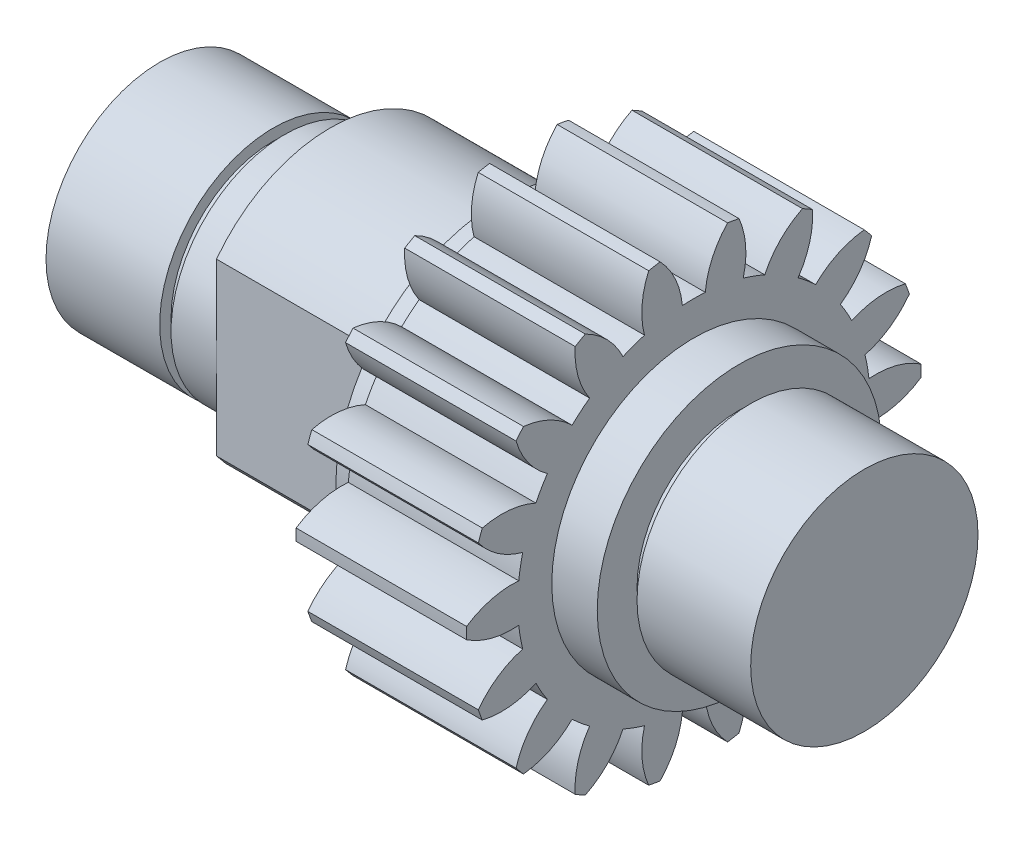
SolidWorks part; units mm, degrees
ref_plane "Plane1" through (0, 0, 0) normal (0, 0, 1) x (1, 0, 0)
ref_plane "Plane2" through (0, 0, 0) normal (0, 1, 0) x (1, 0, 0)
ref_plane "Plane3" through (0, 0, 0) normal (1, 0, 0) x (0, 0, -1)
other "Configuration Table"
sketch "HoldingSke" plane through (0, 0, 0) normal (0, 1, 0) x (1, 0, 0)
  line L0 (0, 0) -> (0.4755, -0.1545)
  line L1 (-15, 0) -> (100, 0) construction
  line L2 (0, 0) -> (-2.1039, 2.3779)
  line L3 (0, 0) -> (-11.863, 4.5341)
  line L4 (0, 0) -> (8.2133, 2.6687)
  line L5 (0, 0) -> (-46.8476, -17.4728)
  line L6 (0, 0) -> (-12.4344, -8.3896)
  line L7 (-2.1039, 2.3779) -> (8.6586, 51.2059)
  line L8 (-76.2, 54.61) -> (-76.1, 54.61)
  line L9 (-71.009, 38.7566) -> (-53.1078, 45.2721)
  line L10 (-76.2, 71.12) -> (104.1128, 71.12)
  line L11 (0, 0) -> (-15, 0)
  line L12 (-76.2, 101.6) -> (-76.133, 101.6)
  line L13 (24.9733, 27.94) -> (52.9518, 28.4284)
  line L14 (24.9733, 27.94) -> (24.9743, 27.94)
  line L15 (24.9733, 27.94) -> (100.4006, 29.5858)
  line L16 (-63.627, -2) -> (-12.827, -2)
  circle A0 centre (0, 0) radius 0.4
  circle A1 centre (0, 0) radius 15.499
  circle A2 centre (0, 0) radius 37.5
  circle A3 centre (0, 0) radius 0.4
  dimension "Num_teeth" = 18
  dimension "Pitch_radius" = 180.3128
  dimension "Width" = 15
  dimension "Thickness" = 15
sketch "BasProSke" plane through (0, 0, 0) normal (0, 1, 0) x (1, 0, 0)
  line L0 (-10, 0) -> (60, 0) construction
  line L1 (0, 0) -> (0, 20)
  line L2 (0, 0) -> (15, 0)
  line L3 (15, 0) -> (15, 20)
  line L4 (15, 20) -> (0, 20)
  dimension "Thickness" = 15
  dimension "Diameter" = 40
revolve "Base-Revolve" add sketch "BasProSke" angle 360 about L0
sketch "TooCutSke" plane through (0, 0, 0) normal (1, 0, 0) x (0, 0, -1)
  line L1 (0, 0) -> (0, 107) construction
  line L2 (0, 0) -> (-1.686, 17.9209) construction
  line L3 (0, 0) -> (-6.231, 35.3376) construction
  line L4 (-1.686, 17.9209) -> (-3.1155, 17.6688) construction
  arc A0 (1.0078, 15.4662) -> (-1.0078, 15.4662) centre (0, 0) ccw
  arc A1 (2.9913, 19.8007) -> (-2.9913, 19.8007) centre (0, 0) ccw
  circle A2 centre (0, 0) radius 18 construction
  circle A3 centre (0, 0) radius 16.9145 construction
  arc A4 (-1.0078, 15.4662) -> (-2.9913, 19.8007) centre (-8.1775, 14.8063) ccw
  arc A5 (2.9913, 19.8007) -> (1.0078, 15.4662) centre (8.1775, 14.8063) ccw
extrude "ToothCut" cut sketch "TooCutSke" along normal through all
fillet "Breaks" [suppressed] radius 0.04 tangent propagation no
fillet "RootFillets" [suppressed] radius 0.501
pattern_circular "TeethCuts" count 18 every 20 about axis through (-10, 0, 0) along (1, 0, 0) of "ToothCut", "RootFillets", "Breaks"
sketch "HubNeaOneSke" plane through (0, 0, 0) normal (-1, 0, 0) x (0, 0, 1)
  circle A0 centre (0, 0) radius 15.499
  dimension "Diameter" = 30.998
extrude "HubNearOne" [suppressed] add sketch "HubNeaOneSke" along normal blind 35.0001
sketch "HubNeaBotSke" plane through (0, 0, 0) normal (-1, 0, 0) x (0, 0, 1)
  circle A0 centre (0, 0) radius 15.499
  dimension "Diameter" = 30.998
extrude "HubNearBoth" [suppressed] add sketch "HubNeaBotSke" along normal blind 17.5
ref_plane "FarPln" through (15, 0, 0) normal (1, 0, 0) x (0, 0, -1)
sketch "HubFarSke" plane through (15, 0, 0) normal (1, 0, 0) x (0, 0, -1)
  circle A0 centre (0, 0) radius 15.499
  dimension "Diameter" = 30.998
extrude "HubFar" [suppressed] add sketch "HubFarSke" along normal blind 17.5
sketch "BorSke" plane through (0, 0, 0) normal (1, 0, 0) x (0, 0, -1)
  circle A0 centre (0, 0) radius 0.4
  dimension "Diameter" = 0.8
extrude "Bore" cut sketch "BorSke" along normal mid plane 100.0001
sketch "KeySke" plane through (0, 0, 0) normal (1, 0, 0) x (0, 0, -1)
  line L0 (-0.05, 0) -> (-0.05, 0.5)
  line L1 (-0.05, 0.5) -> (0.05, 0.5)
  line L2 (0.05, 0.5) -> (0.05, 0)
  line L3 (0, 0) -> (0, 34) construction
  line L4 (-0.05, 0) -> (0.05, 0)
extrude "Keyway" [suppressed] cut sketch "KeySke" along normal mid plane 100.0001
pattern_circular "Keyway2" [suppressed] count 2 every 90 about axis through (-10, 0, 0) along (1, 0, 0)
sketch "Sketch1" plane through (15, 0, 0) normal (1, 0, 0) x (0, 0, -1)
  circle A0 centre (0, 0) radius 12.5
  circle A1 centre (0, 0) radius 10
  dimension "D1" = 25
  dimension "D2" = 20
extrude "Boss-Extrude1" add sketch "Sketch1" along normal blind 4 contours A0
extrude "Boss-Extrude2" add sketch "Sketch1<3>" along normal blind 15 contours A1
sketch "Sketch1<3>" plane through (15, 0, 0) normal (1, 0, 0) x (0, 0, -1) same geometry as "Sketch1"
sketch "Sketch2" plane through (0, 0, 0) normal (0, 0, 1) x (1, 0, 0)
  line L0 (0, 0) -> (31.8545, 0) construction
  line L1 (19, 10) -> (20, 10)
  line L2 (19, 10) -> (19, 9)
  line L3 (19, 9) -> (20, 9)
  line L4 (20, 10) -> (20, 9)
  line L5 (0, 0.5098) -> (0, -0.5098) construction
  dimension "D1" = 1
  dimension "D2" = 18
revolve "Cut-Revolve1" cut sketch "Sketch2" angle 360 about L0
sketch "Sketch3" plane through (0, 0, 0) normal (-1, 0, 0) x (0, 0, 1)
  circle A0 centre (0, 0) radius 14.5
  circle A1 centre (0, 0) radius 12.5
  circle A2 centre (0, 0) radius 10
  dimension "D1" = 29
  dimension "D2" = 25
  dimension "D3" = 20
extrude "Boss-Extrude3" add sketch "Sketch3" along normal blind 2 contours A0
extrude "Boss-Extrude4" add sketch "Sketch3<3>" along normal blind 17 contours A1
sketch "Sketch3<3>" plane through (0, 0, 0) normal (-1, 0, 0) x (0, 0, 1) same geometry as "Sketch3"
extrude "Boss-Extrude5" add sketch "Sketch3<4>" along normal blind 32 contours A2
sketch "Sketch3<4>" plane through (0, 0, 0) normal (-1, 0, 0) x (0, 0, 1) same geometry as "Sketch3"
sketch "Sketch4" plane through (0, 0, 0) normal (0, 0, 1) x (1, 0, 0)
  line L0 (-17, 10) -> (-32, 10) construction
  line L1 (-22, 10) -> (-21, 10)
  line L2 (-22, 10) -> (-22, 9)
  line L3 (-22, 9) -> (-21, 9)
  line L4 (-21, 10) -> (-21, 9)
  line L5 (0, 0) -> (-45.0796, 0) construction
  line L6 (0, 0.5098) -> (0, -0.5098) construction
  line L7 (-32, 10) -> (-32, -10) construction
  dimension "D1" = 1
  dimension "D2" = 10
  dimension "D3" = 18
revolve "Cut-Revolve2" cut sketch "Sketch4" angle 360 about L5
sketch "Sketch5" plane through (-17, 0, 0) normal (-1, 0, 0) x (0, 0, 1)
  line L0 (0, 0) -> (0, -2.8877) construction
  line L1 (-10, 7.5) -> (-10, -7.5)
  line L2 (10, 7.5) -> (10, -7.5)
  circle A0 centre (0, 0) radius 12.5 construction
  arc A1 (-10, -7.5) -> (10, -7.5) centre (0, 0) ccw
  arc A3 (10, 7.5) -> (-10, 7.5) centre (0, 0) ccw
  dimension "D1" = 20
extrude "Cut-Extrude1" cut sketch "Sketch5" against normal up to surface (15 mm away) flip side to cut up to face at (-2, 0, 12.5)
equation "' \"Module@HoldingSke\" = 6.35"
equation "' \"Num_teeth@HoldingSke\" = 12"
equation "' \"Ap@HoldingSke\" =  20"
equation "' \"Ap@HoldingSke\" = 20"
equation "' \"Width@HoldingSke\" = 0.5 * 25.4"
equation "' \"Hub_dia@HoldingSke\"= 1 * 25.4"
equation "' \"Hub_dia@HoldingSke\" = 1 * 25.4"
equation "' \"Overall_len@HoldingSke\" = 1.0 * 25.4"
equation "' \"Bore@HoldingSke\" = 0.75 * 25.4"
equation "' \"T_dim@HoldingSke\" = 0.1 * 25.4"
equation "' \"Width@KeySke\" = 0.25 * 25.4"
equation "' \"Show_teeth@HoldingSke\" = 13"
equation "' \"Backlash@HoldingSke\" = 0.009 * 25.4"
equation "' \"Addendum_fac@HoldingSke\" = 1.0"
equation "' \"Dedendum_fac@HoldingSke\" = 1.25"
equation "' \"Dedendum_add@HoldingSke\" = 0.00005 * 25.4"
equation "' \"Clearance_fac@HoldingSke\" = 0.25"
equation "\"Pitch@HoldingSke\" = 1 / \"Module@HoldingSke\""
equation "\"Overcut_dia@TooCutSke\" = (\"Num_teeth@HoldingSke\" + 2 * \"Addendum_fac@HoldingSke\") / \"Pitch@HoldingSke\" + 0.002 * 25.4"
equation "\"Pitch_dia@TooCutSke\" = \"Num_teeth@HoldingSke\" / \"Pitch@HoldingSke\""
equation "\"Base_dia@TooCutSke\" = \"Num_teeth@HoldingSke\" / \"Pitch@HoldingSke\" * cos((\"Ap@HoldingSke\"  * 3.14159265 / 180))"
equation "\"Root_dia@TooCutSke\" = (\"Num_teeth@HoldingSke\" + 2) / \"Pitch@HoldingSke\" - 2 * (\"Addendum_fac@HoldingSke\" + \"Dedendum_fac@HoldingSke\") / \"Pitch@HoldingSke\" - \"Dedendum_add@HoldingSke\" * 2"
equation "\"Half_ang@TooCutSke\" = 180 / \"Num_teeth@HoldingSke\""
equation "\"Half_CT@TooCutSke\" = \"Num_teeth@HoldingSke\" / \"Pitch@HoldingSke\" * sin((3.14159265 / 2 / \"Num_teeth@HoldingSke\")) / 2 - 7 * \"Backlash@HoldingSke\" / 4"
equation "\"Flank_rad@TooCutSke\" = \"Num_teeth@HoldingSke\" / \"Pitch@HoldingSke\" / 5"
equation "\"Radius@RootFillets\" = \"Clearance_fac@HoldingSke\" / \"Pitch@HoldingSke\" + \"Dedendum_add@HoldingSke\""
equation "\"Break_rad@Breaks\" = 0.02 / \"Pitch@HoldingSke\""
equation "\"Thickness@HoldingSke\" = \"Width@HoldingSke\""
equation "\"OAL@HoldingSke\" = \"Thickness@HoldingSke\""
equation "\"MHD@HoldingSke\" = (\"Num_teeth@HoldingSke\" + 2) / \"Pitch@HoldingSke\" - 2 * (\"Addendum_fac@HoldingSke\" + \"Dedendum_fac@HoldingSke\")  / \"Pitch@HoldingSke\" - \"Dedendum_add@HoldingSke\" * 2"
equation "\"MBD@HoldingSke\" = (\"Num_teeth@HoldingSke\" + 2) / \"Pitch@HoldingSke\" - 2 * (\"Addendum_fac@HoldingSke\" + \"Dedendum_fac@HoldingSke\")  / \"Pitch@HoldingSke\" - \"Dedendum_add@HoldingSke\" * 2 - 0.002 * 25.4"
equation "\"MHD@HoldingSke\" = ((sgn( \"MHD@HoldingSke\" - \"Hub_dia@HoldingSke\" )-1)*( \"MHD@HoldingSke\" - \"Hub_dia@HoldingSke\" ))/-2+ \"Hub_dia@HoldingSke\""
equation "\"MBD@HoldingSke\" = ((sgn( \"MBD@HoldingSke\" - \"Bore@HoldingSke\" )-1)*( \"MBD@HoldingSke\" - \"Bore@HoldingSke\" ))/-2+ \"Bore@HoldingSke\""
equation "\"OAL@HoldingSke\" = ((sgn( \"OAL@HoldingSke\" - \"Overall_len@HoldingSke\" )+1)*( \"OAL@HoldingSke\" - \"Overall_len@HoldingSke\" ))/2 + \"Overall_len@HoldingSke\" + 0.000002 * 25.4"
equation "\"Num_teeth@TeethCuts\" = int( \"Show_teeth@HoldingSke\" ) + 1"
equation "\"Num_teeth@TeethCuts\" = ((sgn( \"Num_teeth@TeethCuts\" - \"Num_teeth@HoldingSke\" )-1)*( \"Num_teeth@TeethCuts\" - \"Num_teeth@HoldingSke\" ))/-2+ \"Num_teeth@HoldingSke\""
equation "\"Num_teeth@TeethCuts\" = ((sgn( \"Num_teeth@TeethCuts\" - 2.0)+1)*( \"Num_teeth@TeethCuts\" - 2.0))/2 +2.0"
equation "\"Angle@TeethCuts\" = 360.0 / \"Num_teeth@HoldingSke\""
equation "\"Diameter@BasProSke\" = (\"Num_teeth@HoldingSke\" + 2 * \"Addendum_fac@HoldingSke\") / \"Pitch@HoldingSke\""
equation "\"Thickness@BasProSke\"  = \"Thickness@HoldingSke\""
equation "' \"Fillet_rad@BasProSke\" =  \"Thickness@HoldingSke\" * 0.05"
equation "' \"Fillet_rad@BasProSke\" = \"Thickness@HoldingSke\" * 0.05"
equation "\"MHD@HoldingSke\" = ((sgn( \"MHD@HoldingSke\" - \"Root_dia@TooCutSke\" )-1)*( \"MHD@HoldingSke\" - \"Root_dia@TooCutSke\" ))/-2+ \"Root_dia@TooCutSke\""
equation "\"Diameter@HubNeaOneSke\" = \"MHD@HoldingSke\""
equation "\"Length@HubNearOne\" = \"OAL@HoldingSke\" - \"Thickness@BasProSke\""
equation "\"Diameter@HubNeaBotSke\" = \"MHD@HoldingSke\""
equation "\"Length@HubNearBoth\" = ( \"OAL@HoldingSke\" - \"Thickness@BasProSke\" ) / 2.0"
equation "\"Thickness@FarPln\" = \"Thickness@BasProSke\""
equation "\"Diameter@HubFarSke\" = \"MHD@HoldingSke\""
equation "\"Length@HubFar\" = ( \"OAL@HoldingSke\" - \"Thickness@BasProSke\" ) / 2.0"
equation "\"Diameter@BorSke\" = \"MBD@HoldingSke\""
equation "\"D1@Bore\" = \"OAL@HoldingSke\" * 2.0"
equation "\"D1@Keyway\" = \"OAL@HoldingSke\" * 2.0"
equation "\"Offset@KeySke\" = \"T_dim@HoldingSke\" + \"MBD@HoldingSke\" / 2.0"
